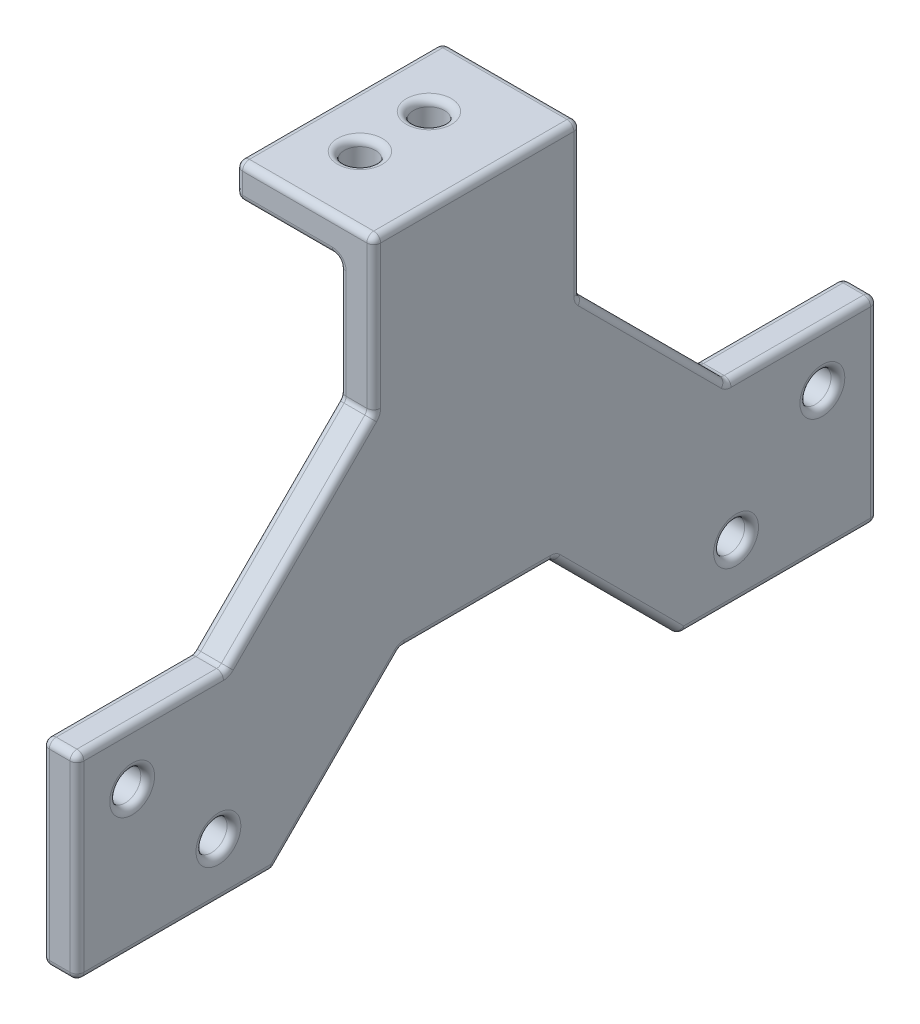
SolidWorks part; units mm, degrees
ref_plane "Front Plane" through (0, 0, 0) normal (0, 0, 1) x (1, 0, 0)
ref_plane "Top Plane" through (0, 0, 0) normal (0, 1, 0) x (1, 0, 0)
ref_plane "Right Plane" through (0, 0, 0) normal (1, 0, 0) x (0, 0, -1)
sketch "Sketch2" plane through (0, 0, 0) normal (1, 0, 0) x (0, 0, -1)
  line L2 (0, 0) -> (0, 28.5)
  line L4 (116, 0) -> (116, 28.5)
  line L5 (43, 72) -> (73, 72)
  line L10 (28.5, 0) -> (47, 18.5)
  line L13 (0, 0) -> (28.5, 0)
  line L14 (87.5, 0) -> (116, 0)
  line L15 (0, 28.5) -> (21.6447, 28.5)
  line L16 (21.6447, 28.5) -> (43, 49.8553)
  line L17 (116, 28.5) -> (94.3553, 28.5)
  line L18 (94.3553, 28.5) -> (73, 49.8553)
  line L19 (73, 72) -> (73, 49.8553)
  line L22 (43, 72) -> (43, 49.8553)
  line L25 (47, 18.5) -> (69, 18.5)
  line L26 (69, 18.5) -> (87.5, 0)
  circle A0 centre (20.5, 8) radius 2.25
  circle A1 centre (8, 20.5) radius 2.25
  circle A2 centre (95.5, 8) radius 2.25
  circle A3 centre (108, 20.5) radius 2.25
  point P17 (68.3645, 47.4198)
  point P19 (43.2178, 43.002)
  point P22 (70.7046, 45.0797)
  point P24 (70.7046, 44.7108)
  dimension "D2" = 30
  dimension "D3" = 72
  dimension "D4" = 4.5
  dimension "D5" = 12.5
  dimension "D6" = 10
  dimension "D7" = 12.5
  dimension "D8" = 12.5
  dimension "D9" = 100
  dimension "D10" = 8
  dimension "D11" = 8
  dimension "D12" = 8
  dimension "D13" = 8
  dimension "D14" = 8
  dimension "D15" = 25
  dimension "D17" = 45
extrude "Boss-Extrude2" add sketch "Sketch2" along normal blind 5
sketch "Sketch3" plane through (0, 0, 0) normal (-1, 0, 0) x (0, 0, 1)
  line L1 (-73, 72) -> (-43, 72)
  line L2 (-73, 72) -> (-73, 67)
  line L3 (-73, 67) -> (-43, 67)
  line L4 (-43, 72) -> (-43, 67)
  line L5 (-73, 49.8553) -> (-73, 72) construction
  line L6 (-43, 72) -> (-43, 49.8553) construction
  line L7 (-73, 72) -> (-43, 72) construction
  dimension "D1" = 5
extrude "Boss-Extrude6" add sketch "Sketch3" along normal blind 15
sketch "Sketch4" plane through (0, 67, 0) normal (0, -1, 0) x (1, 0, 0)
  line L0 (-15, -73) -> (-15, -43) construction
  line L1 (-7, -53) -> (-7, -43) construction
  line L2 (-15, -43) -> (0, -43) construction
  line L3 (-7, -63) -> (-7, -73) construction
  line L4 (-15, -73) -> (0, -73) construction
  circle A0 centre (-7, -53) radius 2.25
  circle A1 centre (-7, -63) radius 2.25
  dimension "D1" = 8
  dimension "D2" = 4.5
  dimension "D3" = 10
extrude "Cut-Extrude1" cut sketch "Sketch4" against normal blind 10
fillet "Fillet5" radius 1 60 edges at (0, 18.5, -58) (0, 39.1777, -32.3223) (0, 39.1777, -83.6777) (2.5, 28.5, -94.3553) (0, 28.5, -105.1777) (2.5, 28.5, -116) (0, 14.25, -116) (2.5, 18.5, -69) (0, 9.25, -78.25) (2.5, 0, -87.5) (2.5, 0, -116) (0, 0, -101.75) (2.5, 18.5, -47) (0, 9.25, -37.75) (2.5, 0, -28.5) (0, 0, -14.25) (2.5, 0, 0) (0, 14.25, 0) (2.5, 28.5, -21.6447) (2.5, 28.5, 0) (0, 28.5, -10.8223) (5, 20.5, -110.25) (5, 20.5, -10.25) (5, 14.25, 0) (5, 28.5, -10.8223) (5, 39.1777, -32.3223) (5, 60.9277, -43) (5, 72, -58) (5, 60.9277, -73) (5, 39.1777, -83.6777) (5, 28.5, -105.1777) (5, 14.25, -116) (5, 0, -101.75) (5, 9.25, -78.25) (5, 18.5, -58) (5, 9.25, -37.75) (5, 0, -14.25) (5, 8, -22.75) (5, 8, -97.75) (0, 8, -97.75) (0, 20.5, -110.25) (0, 20.5, -10.25) (0, 8, -22.75) (-5, 72, -43) (-15, 72, -58) (-5, 72, -73) (-7, 72, -65.25) (-7, 72, -55.25) (-7.5, 67, -73) (-7.5, 67, -43) (0, 67, -58) (-7, 67, -65.25) (-7, 67, -55.25) (-15, 69.5, -43) (-15, 67, -58) (-15, 69.5, -73) (0, 58.4277, -73) (0, 58.4277, -43) (2.5, 49.8553, -43) (2.5, 49.8553, -73)
